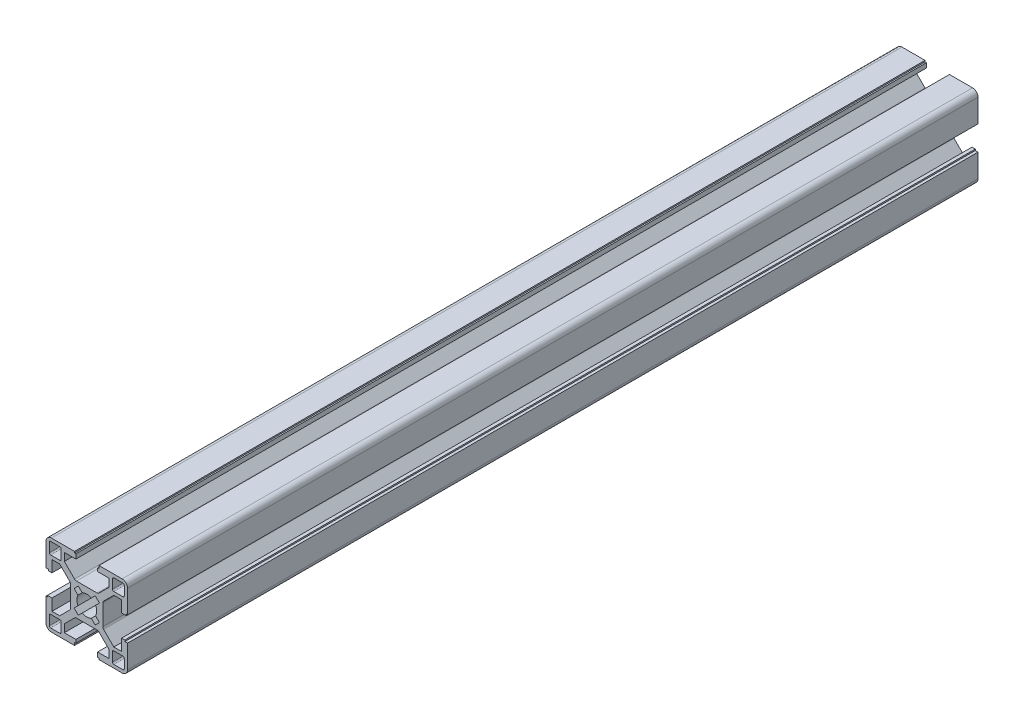
SolidWorks part; units mm, degrees
material "6061-T6 (SS)"
ref_plane "Front Plane" through (0, 0, 0) normal (0, 0, 1) x (1, 0, 0)
ref_plane "Top Plane" through (0, 0, 0) normal (0, 1, 0) x (1, 0, 0)
ref_plane "Right Plane" through (0, 0, 0) normal (1, 0, 0) x (0, 0, -1)
sketch "Sketch1" plane through (0, 0, 0) normal (0, 0, 1) x (1, 0, 0)
  line L0 (-4.5, 15) -> (-4.5, 14.5)
  line L1 (13, -15) -> (4.5, -15)
  line L2 (15, -13) -> (15, -4.5)
  line L3 (13, 15) -> (4.5, 15)
  line L4 (-15, -13) -> (-15, -4.5)
  line L5 (15, -15) -> (-15, 15) construction
  line L6 (15, 15) -> (-15, -15) construction
  line L7 (-4.5, 14.5) -> (-4, 14.5)
  line L8 (-4, 14.5) -> (-4, 12.8)
  line L9 (-4, 12.8) -> (-8.25, 12.8)
  line L10 (-8.25, 12.8) -> (-8.25, 9.95)
  line L11 (-8.25, 9.95) -> (-4.4929, 6.1929)
  line L12 (-3.7858, 5.9) -> (3.7858, 5.9)
  line L13 (4.4929, 6.1929) -> (8.25, 9.95)
  line L14 (8.25, 9.95) -> (8.25, 12.8)
  line L15 (8.25, 12.8) -> (4, 12.8)
  line L16 (4, 12.8) -> (4, 14)
  line L17 (4, 14) -> (4.5, 14)
  line L18 (4.5, 14) -> (4.5, 15)
  line L19 (0, 0) -> (0, 16.8698) construction
  line L20 (-4.5, 15) -> (-13, 15)
  line L21 (12.8, 8.25) -> (9.95, 8.25)
  line L22 (9.95, 8.25) -> (6.1929, 4.4929)
  line L23 (5.9, 3.7858) -> (5.9, -3.7858)
  line L24 (6.1929, -4.4929) -> (9.95, -8.25)
  line L25 (9.95, -8.25) -> (12.8, -8.25)
  line L26 (12.8, -8.25) -> (12.8, -4)
  line L27 (12.8, 4) -> (12.8, 8.25)
  line L28 (12.8, -4) -> (14, -4)
  line L29 (14, -4) -> (14, -4.5)
  line L30 (14, -4.5) -> (15, -4.5)
  line L31 (14.5, 4) -> (12.8, 4)
  line L32 (14.5, 4.5) -> (14.5, 4)
  line L33 (15, 4.5) -> (14.5, 4.5)
  line L34 (8.25, -12.8) -> (8.25, -9.95)
  line L35 (8.25, -9.95) -> (4.4929, -6.1929)
  line L36 (3.7858, -5.9) -> (-3.7858, -5.9)
  line L37 (-4.4929, -6.1929) -> (-8.25, -9.95)
  line L38 (-8.25, -9.95) -> (-8.25, -12.8)
  line L39 (-8.25, -12.8) -> (-4, -12.8)
  line L40 (4, -12.8) -> (8.25, -12.8)
  line L41 (-4, -12.8) -> (-4, -14)
  line L42 (-4, -14) -> (-4.5, -14)
  line L43 (-4.5, -14) -> (-4.5, -15)
  line L44 (4, -14.5) -> (4, -12.8)
  line L45 (4.5, -14.5) -> (4, -14.5)
  line L46 (4.5, -15) -> (4.5, -14.5)
  line L47 (-12.8, -8.25) -> (-9.95, -8.25)
  line L48 (-9.95, -8.25) -> (-6.1929, -4.4929)
  line L49 (-5.9, -3.7858) -> (-5.9, 3.7858)
  line L50 (-6.1929, 4.4929) -> (-9.95, 8.25)
  line L51 (-9.95, 8.25) -> (-12.8, 8.25)
  line L52 (-12.8, 8.25) -> (-12.8, 4)
  line L53 (-12.8, -4) -> (-12.8, -8.25)
  line L54 (-12.8, 4) -> (-14, 4)
  line L55 (-14, 4) -> (-14, 4.5)
  line L56 (-14, 4.5) -> (-15, 4.5)
  line L57 (-14.5, -4) -> (-12.8, -4)
  line L58 (-14.5, -4.5) -> (-14.5, -4)
  line L59 (-15, -4.5) -> (-14.5, -4.5)
  line L60 (15, 4.5) -> (15, 13)
  line L61 (-15, 4.5) -> (-15, 13)
  line L62 (-4.5, -15) -> (-13, -15)
  line L63 (13.3, -9.45) -> (9.95, -9.45)
  line L64 (9.95, 13.8) -> (13.3, 13.8)
  line L65 (9.45, 13.3) -> (9.45, 9.95)
  line L66 (9.95, 9.45) -> (13.3, 9.45)
  line L67 (13.8, 13.3) -> (13.8, 9.95)
  line L68 (13.8, -9.95) -> (13.8, -13.3)
  line L69 (13.3, -13.8) -> (9.95, -13.8)
  line L70 (9.45, -9.95) -> (9.45, -13.3)
  line L71 (-9.45, -13.3) -> (-9.45, -9.95)
  line L72 (-9.95, -13.8) -> (-13.3, -13.8)
  line L73 (-13.8, -13.3) -> (-13.8, -9.95)
  line L74 (-9.95, -9.45) -> (-13.3, -9.45)
  line L75 (-13.3, 9.45) -> (-9.95, 9.45)
  line L76 (-13.8, 9.95) -> (-13.8, 13.3)
  line L77 (-13.3, 13.8) -> (-9.95, 13.8)
  line L78 (-9.45, 9.95) -> (-9.45, 13.3)
  line L79 (-1.6831, -3.2388) -> (-3.1113, -4.6669)
  line L80 (3.1113, 4.6669) -> (4.6669, 3.1113)
  line L81 (4.6669, 3.1113) -> (3.2388, 1.6831)
  line L82 (-3.1113, -4.6669) -> (-4.6669, -3.1113)
  line L83 (-4.6669, -3.1113) -> (-3.2388, -1.6831)
  line L85 (3.1113, -4.6669) -> (4.6669, -3.1113)
  line L86 (3.1113, -4.6669) -> (1.6831, -3.2388)
  line L87 (-4.6669, 3.1113) -> (-3.1113, 4.6669)
  line L88 (-3.1113, 4.6669) -> (-1.6831, 3.2388)
  line L93 (3.2388, -1.6831) -> (4.6669, -3.1113)
  line L95 (1.6831, 3.2388) -> (3.1113, 4.6669)
  line L98 (-3.2388, 1.6831) -> (-4.6669, 3.1113)
  arc A0 (-3.2388, 1.6831) -> (-3.2388, -1.6831) centre (0, 0) ccw
  arc A1 (13, 15) -> (15, 13) centre (13, 13) cw
  arc A2 (15, -13) -> (13, -15) centre (13, -13) cw
  arc A3 (-13, -15) -> (-15, -13) centre (-13, -13) cw
  arc A4 (-15, 13) -> (-13, 15) centre (-13, 13) cw
  arc A5 (-6.1929, 4.4929) -> (-5.9, 3.7858) centre (-6.9, 3.7858) cw
  arc A6 (9.95, 13.8) -> (9.45, 13.3) centre (9.95, 13.3) ccw
  arc A7 (-5.9, -3.7858) -> (-6.1929, -4.4929) centre (-6.9, -3.7858) cw
  arc A8 (-4.4929, -6.1929) -> (-3.7858, -5.9) centre (-3.7858, -6.9) cw
  arc A9 (9.45, 9.95) -> (9.95, 9.45) centre (9.95, 9.95) ccw
  arc A10 (13.8, 9.95) -> (13.3, 9.45) centre (13.3, 9.95) cw
  arc A11 (13.8, 13.3) -> (13.3, 13.8) centre (13.3, 13.3) ccw
  arc A12 (13.8, -9.95) -> (13.3, -9.45) centre (13.3, -9.95) ccw
  arc A13 (13.3, -13.8) -> (13.8, -13.3) centre (13.3, -13.3) ccw
  arc A14 (9.95, -13.8) -> (9.45, -13.3) centre (9.95, -13.3) cw
  arc A15 (9.95, -9.45) -> (9.45, -9.95) centre (9.95, -9.95) ccw
  arc A16 (1.6831, 3.2388) -> (-1.6831, 3.2388) centre (0, 0) ccw
  arc A17 (-9.95, -13.8) -> (-9.45, -13.3) centre (-9.95, -13.3) ccw
  arc A18 (-13.8, -13.3) -> (-13.3, -13.8) centre (-13.3, -13.3) ccw
  arc A19 (-13.8, -9.95) -> (-13.3, -9.45) centre (-13.3, -9.95) cw
  arc A20 (-9.45, -9.95) -> (-9.95, -9.45) centre (-9.95, -9.95) ccw
  arc A21 (1.6831, 3.2388) -> (-1.6831, 3.2388) centre (0, 0) ccw
  arc A22 (-13.8, 9.95) -> (-13.3, 9.45) centre (-13.3, 9.95) ccw
  arc A23 (-13.3, 13.8) -> (-13.8, 13.3) centre (-13.3, 13.3) ccw
  arc A24 (-9.95, 13.8) -> (-9.45, 13.3) centre (-9.95, 13.3) cw
  arc A25 (-9.95, 9.45) -> (-9.45, 9.95) centre (-9.95, 9.95) ccw
  arc A26 (3.2388, -1.6831) -> (3.2388, 1.6831) centre (0, 0) ccw
  arc A27 (3.7858, -5.9) -> (4.4929, -6.1929) centre (3.7858, -6.9) cw
  arc A28 (6.1929, -4.4929) -> (5.9, -3.7858) centre (6.9, -3.7858) cw
  arc A29 (5.9, 3.7858) -> (6.1929, 4.4929) centre (6.9, 3.7858) cw
  arc A30 (4.4929, 6.1929) -> (3.7858, 5.9) centre (3.7858, 6.9) cw
  arc A31 (-3.7858, 5.9) -> (-4.4929, 6.1929) centre (-3.7858, 6.9) cw
  arc A32 (3.2388, -1.6831) -> (3.2388, 1.6831) centre (0, 0) ccw
  arc A33 (-3.2388, 1.6831) -> (-3.2388, -1.6831) centre (0, 0) ccw
  arc A34 (-1.6831, -3.2388) -> (1.6831, -3.2388) centre (0, 0) ccw
  arc A35 (-1.6831, -3.2388) -> (1.6831, -3.2388) centre (0, 0) ccw
  point P0 (0, 0)
  point P70 (0, 0)
  point P135 (0, 0)
  point P144 (4.2, 5.9)
  point P147 (-4.2, 5.9)
  point P151 (0, 0)
  point P154 (3.8891, 3.8891)
  point P159 (0, 0)
  point P162 (3.8891, -3.8891)
  dimension "D18" = 7.3
  dimension "D20" = 2
  dimension "D21" = 1
  dimension "D22" = 1.2
  dimension "D23" = 30
  dimension "D28" = 0.5
  dimension "D1" = 30
  dimension "D2" = 30
  dimension "D3" = 8
  dimension "D4" = 4
  dimension "D5" = 9
  dimension "D6" = 4.5
  dimension "D7" = 1
  dimension "D8" = 0.5
  dimension "D9" = 16.5
  dimension "D10" = 8.25
  dimension "D11" = 2.2
  dimension "D12" = 2.2
  dimension "D13" = 9.1
  dimension "D14" = 2.4042
  dimension "D16" = 45
  dimension "D17" = 45
  dimension "D25" = 1.2
  dimension "D26" = 1.2
  dimension "D27" = 1.2
  dimension "D19" = 4
extrude "Boss-Extrude1" add sketch "Sketch1" along normal blind 313 contours A0 | L75 A25 L78 A24 L77 A23 L76 A22 | L71 A20 L74 A19 L73 A18 L72 A17 | L63 A15 L70 A14 L69 A13 L68 A12 | L67 A11 L64 A6 L65 A9 L66 A10 | L36 A8 L37 L38 L39 L41 L42 L43 L62 A3 L4 L59 L58 L57 L53 L47 L48 A7 L49 A5 L50 L51 L52 L54 L55 L56 L61 A4 L20 L0 L7 L8 L9 L10 L11 A31 L12 A30 L13 L14 L15 L16 L17 L18 L3 A1 L60 L33 L32 L31 L27 L21 L22 A29 L23 A28 L24 L25 L26 L28 L29 L30 L2 A2 L1 L46 L45 L44 L40 L34 L35 A27 region at (11.625, -11.625, 0) region at (11.625, 11.625, 0) region at (-11.625, -11.625, 0) region at (-11.625, 11.625, 0) region at (0, 0, 0)
